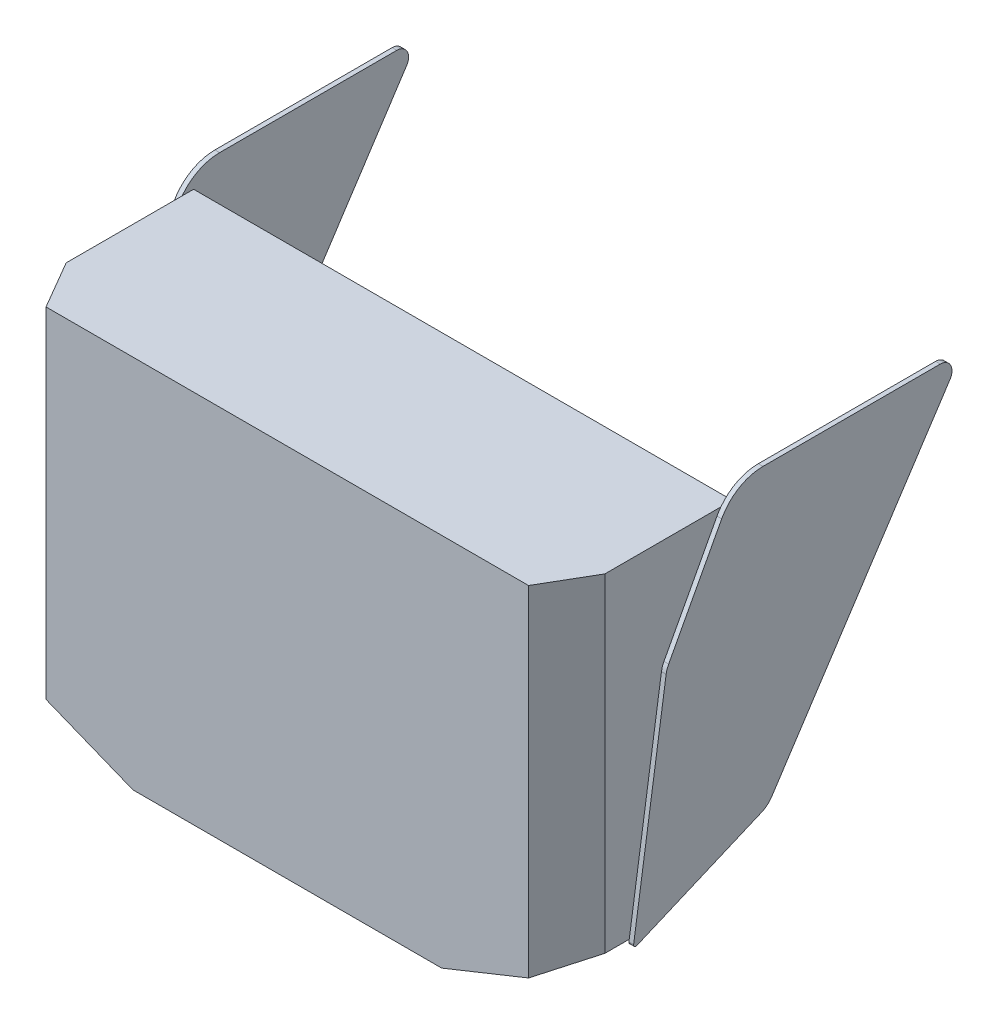
SolidWorks part; units mm, degrees
ref_plane "Front Plane" through (0, 0, 0) normal (0, 0, 1) x (1, 0, 0)
ref_plane "Top Plane" through (0, 0, 0) normal (0, 1, 0) x (1, 0, 0)
ref_plane "Right Plane" through (0, 0, 0) normal (1, 0, 0) x (0, 0, -1)
sketch "Sketch2" plane through (0, 0, 0) normal (0, 0, 1) x (1, 0, 0)
  line L0 (-115, -60.3) -> (-65.9, -80)
  line L1 (65.9, -80) -> (-65.9, -80)
  line L2 (115, -60.3) -> (115, 80)
  line L3 (115, 80) -> (-115, 80)
  line L4 (-115, -60.3) -> (-115, 80)
  line L5 (97.0399, -67.506) -> (-115, 80) construction
  line L6 (115, 80) -> (-97.0399, -67.506) construction
  line L7 (65.9, -80) -> (115, -60.3)
  point P0 (0, 0)
  dimension "D1" = 230
extrude "Boss-Extrude1" add sketch "Sketch2" against normal blind 75
sketch "Sketch3" plane through (0, 0, 0) normal (1, 0, 0) x (0, 0, -1)
  line L0 (0, -80) -> (75, -38.15)
  line L1 (75, 80) -> (75, -60.3) construction
  line L2 (75, -38.15) -> (75, -80)
  line L3 (75, -80) -> (0, -80)
  dimension "D1" = 41.85
extrude "Cut-Extrude1" cut sketch "Sketch3" against normal through all and the other way through all
sketch "Sketch4" plane through (0, 0, 0) normal (0, 1, 0) x (1, 0, 0)
  line L0 (-115, 20.6) -> (-103, 0)
  line L1 (-115, 75) -> (-115, 0) construction
  line L2 (115, 0) -> (-115, 0) construction
  line L3 (-103, 0) -> (-115, 0)
  line L4 (-115, 0) -> (-115, 20.6)
  line L5 (115, 20.6) -> (103, 0)
  line L6 (115, 75) -> (115, 0) construction
  line L7 (103, 0) -> (115, 0)
  line L8 (115, 0) -> (115, 20.6)
  dimension "D1" = 20.6
  dimension "D2" = 12
  dimension "D3" = 12
  dimension "D4" = 20.6
extrude "Cut-Extrude2" cut sketch "Sketch4" against normal through all and the other way through all
sketch "Sketch5" plane through (0, 0, 0) normal (1, 0, 0) x (0, 0, -1)
  line L0 (30.6, -62.9252) -> (88.18, -38.4395)
  line L1 (75, -38.15) -> (35.3047, -60.3) construction
  line L2 (88.18, -38.4395) -> (171.03, 87.9932)
  line L3 (171.03, 87.9932) -> (74.11, 87.9932)
  line L4 (74.11, 87.9932) -> (45, 33.5125)
  line L5 (45, 33.5125) -> (30.6, -62.9252)
  line L6 (20.6, -60.3) -> (20.6, -89.4599) construction
  line L7 (20.6, -60.3) -> (20.6, 80) construction
  dimension "D1" = 10
  dimension "D2" = 24.4
  dimension "D3" = 53.51
  dimension "D4" = 96.92
  dimension "D5" = 151.16
  dimension "D6" = 62.57
  dimension "D7" = 61.77
  dimension "D8" = 67.58
extrude "Boss-Extrude3" add sketch "Sketch5" along direction (1, 0, 0) on the side of the normal blind 2 from offset 115
sketch "Sketch6" plane through (0, 0, 0) normal (1, 0, 0) x (0, 0, -1)
  line L0 (30.6, -62.9252) -> (88.18, -38.4395)
  line L2 (88.18, -38.4395) -> (171.03, 87.9932)
  line L3 (171.03, 87.9932) -> (74.11, 87.9932)
  line L4 (74.11, 87.9932) -> (45, 33.5125)
  line L5 (45, 33.5125) -> (30.6, -62.9252)
  line L6 (20.6, -60.3) -> (20.6, -89.4599) construction
  dimension "D1" = 10
  dimension "D4" = 96.92
  dimension "D5" = 151.16
  dimension "D6" = 62.57
  dimension "D7" = 61.77
extrude "Boss-Extrude5" add sketch "Sketch6" against normal blind 2 from offset 115 offset against normal yes
fillet "Fillet3" radius 5 2 edges at (-116, 87.9932, -171.03) (116, 87.9932, -171.03)
fillet "Fillet4" radius 20 2 edges at (116, 87.9932, -74.11) (-116, 87.9932, -74.11)
fillet "Fillet5" radius 10 1 edges at (116, 33.5125, -45)
fillet "Fillet6" radius 10 1 edges at (-116, -38.4395, -88.18)
fillet "Fillet7" radius 10 1 edges at (-116, 33.5125, -45)
fillet "Fillet8" radius 10 1 edges at (116, -38.4395, -88.18)
fillet "Fillet11" radius 1 2 edges at (-116, -62.9252, -30.6) (116, -62.9252, -30.6)
ref_plane "Plane1" through (0, -80, 0) normal (0, -1, 0) x (-1, 0, 0)
sketch "Sketch7" plane through (0, -80, 0) normal (0, -1, 0) x (-1, 0, 0)
  line L0 (0, 0) -> (0, 75) construction
  line L1 (115, 75) -> (-115, 75) construction
  line L2 (65.9, 0) -> (-65.9, 0) construction
  line L3 (39.94, 0) -> (-39.94, 0)
  line L4 (39.94, 0) -> (39.94, 51.8)
  line L5 (39.94, 51.8) -> (-39.94, 51.8)
  line L6 (-39.94, 0) -> (-39.94, 51.8)
  line L7 (39.94, 0) -> (-39.94, 51.8) construction
  line L8 (39.94, 51.8) -> (-39.94, 0) construction
  point P5 (0, 25.9)
  dimension "D1" = 79.88
  dimension "D2" = 51.8
extrude "Boss-Extrude6" add sketch "Sketch7" against normal up to next
fillet "Fillet13" radius 5 2 edges at (-39.94, -65.5478, -51.8) (39.94, -65.5478, -51.8)
